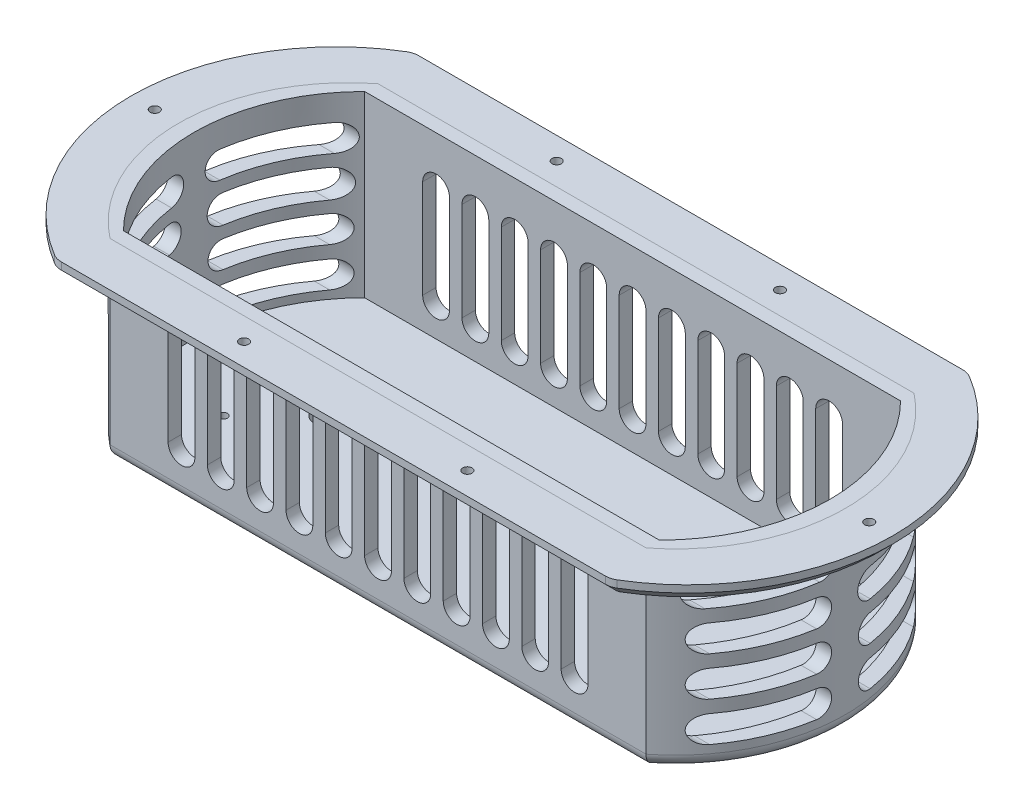
SolidWorks part; units mm, degrees
ref_plane "Front Plane" through (0, 0, 0) normal (0, 0, 1) x (1, 0, 0)
ref_plane "Top Plane" through (0, 0, 0) normal (0, 1, 0) x (1, 0, 0)
ref_plane "Right Plane" through (0, 0, 0) normal (1, 0, 0) x (0, 0, -1)
sketch "Sketch2" plane through (0, 0, 0) normal (0, 1, 0) x (1, 0, 0)
  line L0 (-155, 100) -> (155, 100)
  line L1 (150, 75) -> (-150, 75)
  line L3 (150, -75) -> (-150, -75)
  line L5 (150, 75) -> (-150, -75) construction
  line L6 (150, -75) -> (-150, 75) construction
  line L7 (-155, -100) -> (155, -100)
  line L8 (0, -124.0307) -> (0, 104.3694) construction
  arc A0 (-150, 75) -> (-150, -75) centre (-91.6905, 0) ccw
  arc A1 (150, 75) -> (150, -75) centre (91.6905, 0) cw
  arc A4 (-155, 100) -> (-155, -100) centre (-98.2109, 0) ccw
  arc A5 (155, 100) -> (155, -100) centre (98.2109, 0) cw
  point P0 (0, 0)
  point P14 (0, 100)
  point P17 (0, -100)
  point P18 (0, -75)
  dimension "D3" = 95
  dimension "D4" = 310
  dimension "D8" = 115
  dimension "D1" = 150
  dimension "D2" = 300
  dimension "D5" = 310
  dimension "D6" = 25
  dimension "D7" = 25
extrude "Boss-Extrude1" add sketch "Sketch2" along normal blind 10
sketch "Sketch3" plane through (0, 10, 0) normal (0, 1, 0) x (1, 0, 0)
  line L0 (-150, 75) -> (150, 75)
  line L1 (-150, -75) -> (150, -75)
  line L2 (-155, -100) -> (155, -100)
  line L3 (155, 100) -> (-155, 100)
  line L4 (-155, -100) -> (155, -100)
  line L5 (155, 100) -> (-155, 100)
  arc A1 (-150, 75) -> (-150, -75) centre (-91.6905, 0) ccw
  arc A2 (-155, 100) -> (-155, -100) centre (-98.2109, 0) ccw
  arc A3 (155, -100) -> (155, 100) centre (98.2109, 0) ccw
  arc A4 (-155, 100) -> (-155, -100) centre (-98.2109, 0) ccw
  arc A5 (155, -100) -> (155, 100) centre (98.2109, 0) ccw
  arc A6 (150, 75) -> (150, -75) centre (91.6905, 0) cw
  line M13 (150, -75) -> (-150, -75)
  arc M14 (-150, -75) -> (-150, 75) centre (-91.6905, 0) cw
  line M15 (-150, 75) -> (150, 75)
  arc M16 (150, 75) -> (150, -75) centre (91.6905, 0) cw
  dimension "D1" = 0
extrude "Boss-Extrude2" add sketch "Sketch3" against normal blind 100 separate body contours M13 M16 M15 M14 region at (0, 10, 0)
sketch "Sketch6" plane through (0, 10, 0) normal (0, 1, 0) x (-1, 0, 0)
  line L1 (120, 67.5) -> (-120, 67.5)
  line L3 (120, -67.5) -> (-120, -67.5)
  line L5 (120, 67.5) -> (-120, -67.5) construction
  line L6 (120, -67.5) -> (-120, 67.5) construction
  arc A0 (120, 67.5) -> (120, -67.5) centre (68.3401, 0) cw
  arc A1 (-120, 67.5) -> (-120, -67.5) centre (-68.3401, 0) ccw
  point P0 (0, 0)
  dimension "D3" = 85
  dimension "D1" = 240
  dimension "D2" = 135
extrude "Cut-Extrude1" cut sketch "Sketch6" against normal blind 85
fillet "Fillet2" radius 10 4 edges at (-155, 5, 100) (155, 5, 100) (-155, 5, -100) (155, 5, -100)
sketch "Sketch10" plane through (0, 0, 0) normal (0, -1, 0) x (1, 0, 0)
  line L0 (-125, 87.5) -> (125, 87.5) construction
  line L1 (-125, -87.5) -> (125, -87.5) construction
  line L2 (-152.2942, 100) -> (152.2942, 100) construction
  line L5 (150, -75) -> (-150, -75) construction
  line L6 (0, -31.9019) -> (0, -178.1053) construction
  line L7 (0, 118.6966) -> (0, 41.5647) construction
  line L8 (-150, 75) -> (150, 75) construction
  circle A0 centre (-199.9509, 0) radius 4.6
  circle A1 centre (199.9505, 0) radius 4.6
  circle A2 centre (-62.5, 87.5) radius 4.6
  circle A3 centre (62.5, 87.5) radius 4.6
  circle A4 centre (-62.5, -87.5) radius 4.6
  circle A5 centre (62.5, -87.5) radius 4.6
  arc A11 (-157.445, 98.5714) -> (-157.445, -98.5714) centre (-98.2109, 0) ccw construction
  arc A13 (150, -75) -> (150, 75) centre (91.6905, 0) ccw construction
  point P19 (-213.2109, 0)
  point P27 (186.6905, 0)
  point P31 (0, -87.5)
  point P32 (0, -75)
  point P35 (0, 87.5)
  point P38 (0, 75)
  dimension "D1" = 9.2
  dimension "D2" = 13.26
  dimension "D3" = 13.26
  dimension "D4" = 12.5
  dimension "D5" = 12.5
  dimension "D6" = 250
  dimension "D7" = 62.5
  dimension "D8" = 62.5
  dimension "D9" = 250
  dimension "D10" = 62.5
  dimension "D11" = 62.5
extrude "Cut-Extrude2" cut sketch "Sketch10" against normal blind 5 contours A0
extrude "Cut-Extrude3" cut sketch "Sketch10<3>" against normal blind 5 contours A4
sketch "Sketch10<3>" plane through (0, 0, 0) normal (0, -1, 0) x (1, 0, 0) same geometry as "Sketch10"
extrude "Cut-Extrude4" cut sketch "Sketch10<4>" against normal blind 5 contours A5
sketch "Sketch10<4>" plane through (0, 0, 0) normal (0, -1, 0) x (1, 0, 0) same geometry as "Sketch10"
extrude "Cut-Extrude5" cut sketch "Sketch10<5>" against normal blind 5 contours A1
sketch "Sketch10<5>" plane through (0, 0, 0) normal (0, -1, 0) x (1, 0, 0) same geometry as "Sketch10"
extrude "Cut-Extrude6" cut sketch "Sketch10<6>" against normal blind 5 contours A2
sketch "Sketch10<6>" plane through (0, 0, 0) normal (0, -1, 0) x (1, 0, 0) same geometry as "Sketch10"
extrude "Cut-Extrude7" cut sketch "Sketch10<7>" against normal blind 5 contours A3
sketch "Sketch10<7>" plane through (0, 0, 0) normal (0, -1, 0) x (1, 0, 0) same geometry as "Sketch10"
sketch "Sketch12" plane through (0, 5, 0) normal (0, -1, 0) x (1, 0, 0)
  circle A0 centre (-199.9509, 0) radius 2.6
  circle A1 centre (-62.5, 87.5) radius 2.6
  circle A2 centre (62.5, 87.5) radius 2.6
  circle A3 centre (199.9505, 0) radius 2.6
  circle A4 centre (62.5, -87.5) radius 2.6
  circle A5 centre (-62.5, -87.5) radius 2.6
  dimension "D1" = 5.2
extrude "Cut-Extrude8" cut sketch "Sketch12" against normal blind 5 contours A0
extrude "Cut-Extrude9" cut sketch "Sketch12<3>" against normal blind 5 contours A1
sketch "Sketch12<3>" plane through (0, 5, 0) normal (0, -1, 0) x (1, 0, 0) same geometry as "Sketch12"
extrude "Cut-Extrude10" cut sketch "Sketch12<4>" against normal blind 5 contours A2
sketch "Sketch12<4>" plane through (0, 5, 0) normal (0, -1, 0) x (1, 0, 0) same geometry as "Sketch12"
extrude "Cut-Extrude11" cut sketch "Sketch12<5>" against normal blind 5 contours A3
sketch "Sketch12<5>" plane through (0, 5, 0) normal (0, -1, 0) x (1, 0, 0) same geometry as "Sketch12"
extrude "Cut-Extrude12" cut sketch "Sketch12<6>" against normal blind 5 contours A5
sketch "Sketch12<6>" plane through (0, 5, 0) normal (0, -1, 0) x (1, 0, 0) same geometry as "Sketch12"
extrude "Cut-Extrude13" cut sketch "Sketch12<7>" against normal blind 5 contours A4
sketch "Sketch12<7>" plane through (0, 5, 0) normal (0, -1, 0) x (1, 0, 0) same geometry as "Sketch12"
sketch "Sketch35" plane through (0, -90, 0) normal (0, -1, 0) x (1, 0, 0)
  line L2 (150, 75) -> (-150, 75)
  line L3 (-150, -75) -> (150, -75)
  line L4 (150, 75) -> (-150, 75)
  line L5 (-150, -75) -> (150, -75)
  arc A2 (-150, 75) -> (-150, -75) centre (-91.6905, 0) ccw
  arc A3 (150, -75) -> (150, 75) centre (91.6905, 0) ccw
  arc A4 (-150, 75) -> (-150, -75) centre (-91.6905, 0) ccw
  arc A5 (150, -75) -> (150, 75) centre (91.6905, 0) ccw
  dimension "D1" = 0
extrude "Boss-Extrude3" add sketch "Sketch35" along normal blind 7.5
fillet "Fillet4" radius 7.5 4 edges at (0, -97.5, -75) (-186.6905, -97.5, 0) (0, -97.5, 75) (186.6905, -97.5, 0)
sketch "Sketch39" plane through (0, -75, 0) normal (0, 1, 0) x (1, 0, 0)
  line L2 (120, 67.5) -> (-120, 67.5)
  line L3 (-120, -67.5) -> (120, -67.5)
  line L4 (120, 67.5) -> (-120, 67.5)
  line L5 (-120, -67.5) -> (120, -67.5)
  arc A2 (120, -67.5) -> (120, 67.5) centre (68.3401, 0) ccw
  arc A3 (-120, 67.5) -> (-120, -67.5) centre (-68.3401, 0) ccw
  arc A4 (120, -67.5) -> (120, 67.5) centre (68.3401, 0) ccw
  arc A5 (-120, 67.5) -> (-120, -67.5) centre (-68.3401, 0) ccw
  dimension "D1" = 0
extrude "Cut-Extrude17" cut sketch "Sketch39" against normal blind 15
sketch "Sketch40" plane through (0, 0, -75) normal (0, 0, -1) x (-1, 0, 0)
  line L0 (0, 0) -> (0, -90) construction
  line L1 (-150, -90) -> (150, -90) construction
  line L2 (-150, -45) -> (150, -45) construction
  line L3 (-150, -90) -> (-150, 10) construction
  line L4 (150, -90) -> (150, 10) construction
  line L5 (0, -17.5) -> (0, -72.5) construction
  line L6 (7.5, -17.5) -> (7.5, -72.5)
  line L7 (-7.5, -17.5) -> (-7.5, -72.5)
  line L8 (14.5, -17.5) -> (14.5, -72.5)
  line L9 (29.5, -17.5) -> (29.5, -72.5)
  line L10 (22, -17.5) -> (22, -72.5) construction
  line L11 (36.5, -17.5) -> (36.5, -72.5)
  line L12 (51.5, -17.5) -> (51.5, -72.5)
  line L13 (44, -17.5) -> (44, -72.5) construction
  line L14 (58.5, -17.5) -> (58.5, -72.5)
  line L15 (73.5, -17.5) -> (73.5, -72.5)
  line L16 (66, -17.5) -> (66, -72.5) construction
  line L17 (80.5, -17.5) -> (80.5, -72.5)
  line L18 (95.5, -17.5) -> (95.5, -72.5)
  line L19 (88, -17.5) -> (88, -72.5) construction
  line L20 (102.5, -17.5) -> (102.5, -72.5)
  line L21 (117.5, -17.5) -> (117.5, -72.5)
  line L22 (110, -17.5) -> (110, -72.5) construction
  line L23 (-29.5, -17.5) -> (-29.5, -72.5)
  line L24 (-14.5, -17.5) -> (-14.5, -72.5)
  line L25 (-22, -17.5) -> (-22, -72.5) construction
  line L26 (-51.5, -17.5) -> (-51.5, -72.5)
  line L27 (-36.5, -17.5) -> (-36.5, -72.5)
  line L28 (-44, -17.5) -> (-44, -72.5) construction
  line L29 (-73.5, -17.5) -> (-73.5, -72.5)
  line L30 (-58.5, -17.5) -> (-58.5, -72.5)
  line L31 (-66, -17.5) -> (-66, -72.5) construction
  line L32 (-95.5, -17.5) -> (-95.5, -72.5)
  line L33 (-80.5, -17.5) -> (-80.5, -72.5)
  line L34 (-88, -17.5) -> (-88, -72.5) construction
  line L35 (-117.5, -17.5) -> (-117.5, -72.5)
  line L36 (-102.5, -17.5) -> (-102.5, -72.5)
  line L37 (-110, -17.5) -> (-110, -72.5) construction
  arc A0 (7.5, -17.5) -> (-7.5, -17.5) centre (0, -17.5) ccw
  arc A1 (-7.5, -72.5) -> (7.5, -72.5) centre (0, -72.5) ccw
  arc A2 (29.5, -17.5) -> (14.5, -17.5) centre (22, -17.5) ccw
  arc A3 (14.5, -72.5) -> (29.5, -72.5) centre (22, -72.5) ccw
  arc A4 (51.5, -17.5) -> (36.5, -17.5) centre (44, -17.5) ccw
  arc A5 (36.5, -72.5) -> (51.5, -72.5) centre (44, -72.5) ccw
  arc A6 (73.5, -17.5) -> (58.5, -17.5) centre (66, -17.5) ccw
  arc A7 (58.5, -72.5) -> (73.5, -72.5) centre (66, -72.5) ccw
  arc A8 (95.5, -17.5) -> (80.5, -17.5) centre (88, -17.5) ccw
  arc A9 (80.5, -72.5) -> (95.5, -72.5) centre (88, -72.5) ccw
  arc A10 (117.5, -17.5) -> (102.5, -17.5) centre (110, -17.5) ccw
  arc A11 (102.5, -72.5) -> (117.5, -72.5) centre (110, -72.5) ccw
  arc A12 (-14.5, -17.5) -> (-29.5, -17.5) centre (-22, -17.5) ccw
  arc A13 (-29.5, -72.5) -> (-14.5, -72.5) centre (-22, -72.5) ccw
  arc A14 (-36.5, -17.5) -> (-51.5, -17.5) centre (-44, -17.5) ccw
  arc A15 (-51.5, -72.5) -> (-36.5, -72.5) centre (-44, -72.5) ccw
  arc A16 (-58.5, -17.5) -> (-73.5, -17.5) centre (-66, -17.5) ccw
  arc A17 (-73.5, -72.5) -> (-58.5, -72.5) centre (-66, -72.5) ccw
  arc A18 (-80.5, -17.5) -> (-95.5, -17.5) centre (-88, -17.5) ccw
  arc A19 (-95.5, -72.5) -> (-80.5, -72.5) centre (-88, -72.5) ccw
  arc A20 (-102.5, -17.5) -> (-117.5, -17.5) centre (-110, -17.5) ccw
  arc A21 (-117.5, -72.5) -> (-102.5, -72.5) centre (-110, -72.5) ccw
  point P3 (0, -45)
  point P14 (0, -45)
  point P23 (22, -45)
  point P30 (44, -45)
  point P37 (66, -45)
  point P44 (88, -45)
  point P51 (110, -45)
  point P57 (-22, -45)
  point P64 (-44, -45)
  point P71 (-66, -45)
  point P78 (-88, -45)
  point P85 (-110, -45)
  dimension "D1" = 15
  dimension "D2" = 55
  dimension "D3" = 6
  dimension "D4" = 6
extrude "Cut-Extrude19" cut sketch "Sketch40" against normal through all
sketch "Sketch46" plane through (0, -97.5, 0) normal (0, -1, 0) x (1, 0, 0)
  line L0 (0, 0) -> (-144.535, 0) construction
  line L1 (-147.3681, 67.5) -> (-147.3681, -67.5) construction
  line L3 (-132.3681, 29.26) -> (-73.8481, 29.26) construction
  line L4 (-132.3681, 29.26) -> (-132.3681, -29.26) construction
  line L5 (-132.3681, -29.26) -> (-73.8481, -29.26) construction
  line L6 (-73.8481, 29.26) -> (-73.8481, -29.26) construction
  line L7 (-132.3681, 29.26) -> (-73.8481, -29.26) construction
  line L8 (-132.3681, -29.26) -> (-73.8481, 29.26) construction
  circle A0 centre (-132.3681, 29.26) radius 2.35
  circle A1 centre (-73.8481, 29.26) radius 2.35
  circle A2 centre (-73.8481, -29.26) radius 2.35
  circle A3 centre (-132.3681, -29.26) radius 2.35
  point P5 (-103.1081, 0)
  dimension "D4" = 4.7
  dimension "D1" = 58.52
  dimension "D2" = 58.52
  dimension "D3" = 15
extrude "Cut-Extrude20" cut sketch "Sketch46" against normal blind 10
sketch "Sketch48" plane through (0, 0, 0) normal (1, 0, 0) x (0, 0, -1)
  line L0 (0, 0) -> (0, -90) construction
  line L1 (-75, -90) -> (75, -90) construction
  line L2 (-75, -45) -> (75, -45) construction
  line L3 (-75, -90) -> (-75, 10) construction
  line L4 (75, -90) -> (75, 10) construction
  line L5 (-58.5, -12) -> (-13.5, -12) construction
  line L6 (-58.5, -4.5) -> (-13.5, -4.5)
  line L7 (-58.5, -19.5) -> (-13.5, -19.5)
  line L8 (13.5, -12) -> (58.5, -12) construction
  line L9 (13.5, -4.5) -> (58.5, -4.5)
  line L10 (13.5, -19.5) -> (58.5, -19.5)
  line L11 (-57, -34) -> (-15, -34) construction
  line L12 (-57, -26.5) -> (-15, -26.5)
  line L13 (-57, -41.5) -> (-15, -41.5)
  line L14 (15, -34) -> (57, -34) construction
  line L15 (15, -26.0734) -> (57, -26.0734)
  line L16 (15, -41.9266) -> (57, -41.9266)
  line L17 (-57, -56) -> (-15, -56) construction
  line L18 (-57, -48.5) -> (-15, -48.5)
  line L19 (-57, -63.5) -> (-15, -63.5)
  line L20 (15, -56) -> (57, -56) construction
  line L21 (15, -48.5) -> (57, -48.5)
  line L22 (15, -63.5) -> (57, -63.5)
  line L23 (-57, -78) -> (-15, -78) construction
  line L24 (-57, -70.5) -> (-15, -70.5)
  line L25 (-57, -85.5) -> (-15, -85.5)
  line L26 (15, -78) -> (57, -78) construction
  line L27 (15, -70.5) -> (57, -70.5)
  line L28 (15, -85.5) -> (57, -85.5)
  arc A0 (-58.5, -4.5) -> (-58.5, -19.5) centre (-58.5, -12) ccw
  arc A1 (-13.5, -19.5) -> (-13.5, -4.5) centre (-13.5, -12) ccw
  arc A2 (13.5, -4.5) -> (13.5, -19.5) centre (13.5, -12) ccw
  arc A3 (58.5, -19.5) -> (58.5, -4.5) centre (58.5, -12) ccw
  arc A4 (-57, -26.5) -> (-57, -41.5) centre (-57, -34) ccw
  arc A5 (-15, -41.5) -> (-15, -26.5) centre (-15, -34) ccw
  arc A6 (15, -26.0734) -> (15, -41.9266) centre (15, -34) ccw
  arc A7 (57, -41.9266) -> (57, -26.0734) centre (57, -34) ccw
  arc A8 (-57, -48.5) -> (-57, -63.5) centre (-57, -56) ccw
  arc A9 (-15, -63.5) -> (-15, -48.5) centre (-15, -56) ccw
  arc A10 (15, -48.5) -> (15, -63.5) centre (15, -56) ccw
  arc A11 (57, -63.5) -> (57, -48.5) centre (57, -56) ccw
  arc A12 (-57, -70.5) -> (-57, -85.5) centre (-57, -78) ccw
  arc A13 (-15, -85.5) -> (-15, -70.5) centre (-15, -78) ccw
  arc A14 (15, -70.5) -> (15, -85.5) centre (15, -78) ccw
  arc A15 (57, -85.5) -> (57, -70.5) centre (57, -78) ccw
  point P13 (-36, -12)
  point P18 (36, -12)
  point P25 (0, -45)
  point P28 (-36, -34)
  point P33 (36, -34)
  point P42 (-36, -56)
  point P47 (36, -56)
  point P54 (-36, -78)
  point P61 (36, -78)
  dimension "D1" = 45
  dimension "D2" = 39
  dimension "D3" = 15
  dimension "D4" = 15
  dimension "D5" = 39
  dimension "D6" = 15
  dimension "D7" = 15
  dimension "D8" = 7
  dimension "D9" = 7
  dimension "D10" = 7
  dimension "D11" = 4.5
extrude "Cut-Extrude21" cut sketch "Sketch48" against normal mid plane 380
chamfer "Chamfer1" distance 6 angle 45 8 edges at (213.2109, 0, 0) (154.9668, 0, -99.6362) (154.9668, 0, 99.6362) (0, 0, -100) (0, 0, 100) (-154.9668, 0, -99.6362) (-154.9668, 0, 99.6362) (-213.2109, 0, 0)
sketch "Sketch50" plane through (0, 10, 0) normal (0, 1, 0) x (1, 0, 0)
  line L0 (-120, 67.5) -> (-150, 67.5)
  line L1 (-120, -67.5) -> (-150, -67.5)
  line L2 (120, 67.5) -> (150, 67.5)
  line L3 (120, -67.5) -> (150, -67.5)
  arc A0 (-120, 67.5) -> (-120, -67.5) centre (-68.3401, 0) ccw
  arc A1 (-150, 67.5) -> (-150, -67.5) centre (-82.5, 0) ccw
  arc A2 (120, 67.5) -> (120, -67.5) centre (68.3401, 0) cw
  arc A3 (150, 67.5) -> (150, -67.5) centre (82.5, 0) cw
  dimension "D1" = 30
  dimension "D2" = 30
extrude "Cut-Extrude23" cut sketch "Sketch50" against normal up to surface (100 mm away) up to face at (-132.3681, -90, -26.91)
sketch "Sketch52" plane through (0, -97.5, 0) normal (0, -1, 0) x (1, 0, 0)
  line L0 (-132.3681, 29.26) -> (-73.8481, -29.26) construction
  line L1 (-73.8481, 29.26) -> (-132.3681, -29.26) construction
  circle A0 centre (-103.1081, 0) radius 7.5
  dimension "D1" = 15
extrude "Cut-Extrude26" cut sketch "Sketch52" against normal through all both
ref_plane "Plane1" through (0, 20, 0) normal (0, 1, 0) x (1, 0, 0)
sketch "Sketch53" plane through (0, 20, 0) normal (0, 1, 0) x (1, 0, 0)
  circle A0 centre (-103.1081, 0) radius 7.5 construction
  circle A1 centre (-103.1081, 0) radius 7.5 construction
